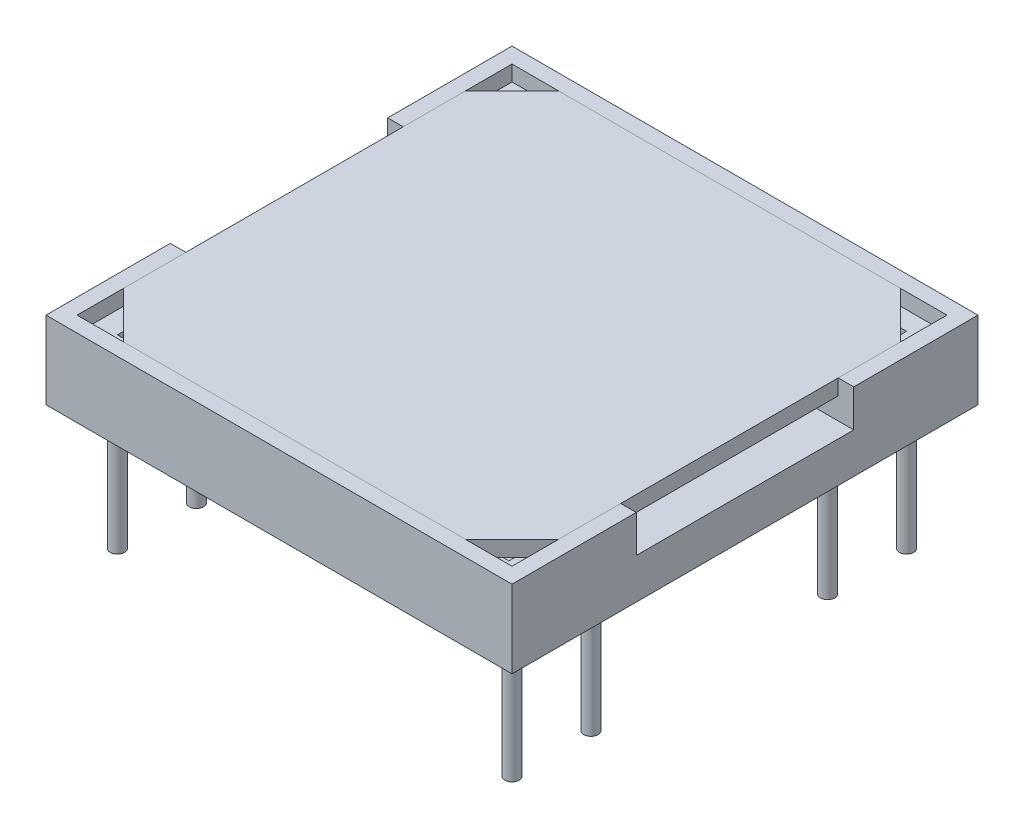
SolidWorks part; units mm, degrees
ref_plane "Front Plane" through (0, 0, 0) normal (0, 0, 1) x (1, 0, 0)
ref_plane "Top Plane" through (0, 0, 0) normal (0, 1, 0) x (1, 0, 0)
ref_plane "Right Plane" through (0, 0, 0) normal (1, 0, 0) x (0, 0, -1)
sketch "Sketch1" plane through (0, 0, 0) normal (0, 1, 0) x (1, 0, 0)
  line L0 (0, 0) -> (0, 7.5) construction
  line L1 (-7.5, -7.5) -> (7.5, -7.5)
  line L2 (-7.5, -7.5) -> (-7.5, 7.5)
  line L3 (-7.5, 7.5) -> (7.5, 7.5)
  line L4 (7.5, -7.5) -> (7.5, 7.5)
  line L5 (0, 0) -> (-7.5, 0) construction
  line L6 (-0.05, 6.4) -> (0, 6.4) construction
  line L7 (-6.3, 6.4) -> (-0.05, 6.4)
  line L8 (-6.3, 6.4) -> (-6.3, 0.05)
  line L9 (-6.3, 0.05) -> (-0.05, 0.05)
  line L10 (-0.05, 6.4) -> (-0.05, 0.05)
  line L23 (-6.3, 0.05) -> (-6.3, 0) construction
  line L24 (-6.1, 0.25) -> (-6.1, 0.05) construction
  line L25 (-6.3, 6.4) -> (-6.3, 7.5) construction
  line L26 (-6.1, 6.2) -> (-0.25, 6.2)
  line L27 (-6.1, 6.2) -> (-6.1, 0.25)
  line L28 (-6.1, 0.25) -> (-0.25, 0.25)
  line L29 (-0.25, 6.2) -> (-0.25, 0.25)
  line L30 (-0.25, 6.2) -> (-0.05, 6.2) construction
  line L31 (-0.25, -6.2) -> (-0.25, -0.25)
  line L32 (-6.1, -0.25) -> (-0.25, -0.25)
  line L33 (-6.1, -6.2) -> (-6.1, -0.25)
  line L34 (-6.1, -6.2) -> (-0.25, -6.2)
  line L35 (-0.05, -6.4) -> (-0.05, -0.05)
  line L36 (-6.3, -0.05) -> (-0.05, -0.05)
  line L37 (-6.3, -6.4) -> (-6.3, -0.05)
  line L38 (-6.3, -6.4) -> (-0.05, -6.4)
  line L39 (6.3, -6.4) -> (0.05, -6.4)
  line L40 (6.1, -6.2) -> (0.25, -6.2)
  line L41 (6.1, -0.25) -> (0.25, -0.25)
  line L42 (6.3, -0.05) -> (0.05, -0.05)
  line L43 (6.3, 0.05) -> (0.05, 0.05)
  line L44 (6.1, 0.25) -> (0.25, 0.25)
  line L45 (6.1, 6.2) -> (0.25, 6.2)
  line L46 (6.3, 6.4) -> (0.05, 6.4)
  line L47 (6.1, 6.2) -> (6.1, 0.25)
  line L48 (0.25, 6.2) -> (0.25, 0.25)
  line L49 (0.05, 6.4) -> (0.05, 0.05)
  line L50 (0.05, -6.4) -> (0.05, -0.05)
  line L51 (0.25, -6.2) -> (0.25, -0.25)
  line L52 (6.1, -6.2) -> (6.1, -0.25)
  line L53 (6.3, -6.4) -> (6.3, -0.05)
  line L54 (6.3, 6.4) -> (6.3, 0.05)
  line L55 (-7, -7) -> (-7, 7)
  line L56 (-7, 7) -> (7, 7)
  line L57 (-7, -7) -> (7, -7)
  line L58 (7, -7) -> (7, 7)
  line L59 (-7.5, 3.5) -> (-6.3, 3.5)
  line L60 (-7.5, -3.5) -> (-6.3, -3.5)
  line L61 (7.5, -3.5) -> (6.3, -3.5)
  line L62 (7.5, 3.5) -> (6.3, 3.5)
  line L63 (-6.3, 0.05) -> (-6.3, -0.05)
  line L64 (6.3, 0.05) -> (6.3, -0.05)
  line L65 (-0.05, 6.4) -> (0.05, 6.4)
  line L66 (-0.05, -6.4) -> (0.05, -6.4)
  point P49 (-7, 0)
  point P51 (0, -7)
  point P52 (0, 7)
  dimension "D1" = 7.5
  dimension "D2" = 7.5
  dimension "D3" = 0.2
  dimension "D4" = 0.25
  dimension "D5" = 0.2
  dimension "D6" = 6.35
  dimension "D7" = 6.25
  dimension "D8" = 0.25
  dimension "D9" = 5.95
  dimension "D10" = 5.85
  dimension "D11" = 7
  dimension "D12" = 7
  dimension "D13" = 3.5
extrude "Boss-Extrude1" add sketch "Sketch1" along normal blind 0.61 contours L2 L3 L4 L1
extrude "Boss-Extrude2" add sketch "Sketch1<3>" along normal blind 0.69 from surface contours L29 L26 L27 L28 | L45 L48 L44 L47 | L40 L52 L41 L51 | L33 L34 L31 L32 region at (-3.175, 0, -3.225) region at (-3.175, 0, 3.225) region at (3.175, 0, 3.225) region at (3.175, 0, -3.225) starting at face at (0, 0.61, 0)
sketch "Sketch1<3>" plane through (0, 0, 0) normal (0, 1, 0) x (1, 0, 0) same geometry as "Sketch1"
extrude "Boss-Extrude3" add sketch "Sketch1<4>" along normal blind 1.39 from surface contours L62 L4 L3 L2 L59 L55 L56 L58 | L7 L65 L46 L54 L62 L58 L56 L55 L59 L8 | L2 L60 L55 L59 | L63 L8 L59 L55 L60 L37 | L4 L61 L58 L57 L55 L60 L2 L1 | L66 L38 L37 L60 L55 L57 L58 L61 L53 L39 | L54 L64 L53 L61 L58 L62 | L4 L62 L58 L61 region at (-7.3448, 0, 5.5) region at (-7.25, 0, 0) region at (7.25, 0, 0) region at (-7.3448, 0, -5.5) region at (-6.65, 0, 3.6443) region at (-6.65, 0, 0) region at (6.65, 0, 0) region at (-6.8557, 0, -5.25) starting at face at (-3.175, 0.61, 3.225)
sketch "Sketch1<4>" plane through (0, 0, 0) normal (0, 1, 0) x (1, 0, 0) same geometry as "Sketch1"
extrude "Boss-Extrude4" add sketch "Sketch1<7>" along normal blind 0.5 from surface contours L62 L4 L3 L2 L59 L55 L56 L58 | L2 L60 L55 L59 | L4 L61 L58 L57 L55 L60 L2 L1 | L4 L62 L58 L61 region at (-7.3448, 0, 5.5) region at (-7.25, 0, 0) region at (7.25, 0, 0) region at (-7.3448, 0, -5.5) starting at face at (0, 2, 0)
sketch "Sketch1<7>" plane through (0, 0, 0) normal (0, 1, 0) x (1, 0, 0) same geometry as "Sketch1"
extrude "Cut-Extrude1" cut sketch "Sketch1<6>" against normal blind 1.2 from surface contours L2 L60 L55 L59 | L4 L62 L58 L61 | L63 L8 L59 L55 L60 L37 | L54 L64 L53 L61 L58 L62 region at (-7.25, 0, 0) region at (7.25, 0, 0) region at (-6.65, 0, 0) region at (6.65, 0, 0) starting at face at (0, 2.5, 0)
sketch "Sketch1<6>" plane through (0, 0, 0) normal (0, 1, 0) x (1, 0, 0) same geometry as "Sketch1"
sketch "Sketch2" plane through (0, 0, 0) normal (0, -1, 0) x (1, 0, 0)
  line L0 (0, 0) -> (0, 7.5) construction
  line L1 (-7.5, 7.5) -> (7.5, 7.5) construction
  line L2 (0, 0) -> (7.5, 0) construction
  line L3 (7.5, 7.5) -> (7.5, -7.5) construction
  line L4 (6.35, 6.35) -> (6.35, 3.81) construction
  line L5 (6.35, 3.81) -> (6.35, 0) construction
  circle A0 centre (6.35, 6.35) radius 0.23
  circle A1 centre (6.35, 3.81) radius 0.23
  circle A2 centre (-6.35, 3.81) radius 0.23
  circle A3 centre (-6.35, 6.35) radius 0.23
  circle A4 centre (6.35, -3.81) radius 0.23
  circle A5 centre (6.35, -6.35) radius 0.23
  circle A6 centre (-6.35, -6.35) radius 0.23
  circle A7 centre (-6.35, -3.81) radius 0.23
  dimension "D4" = 0.46
  dimension "D1" = 2.54
  dimension "D2" = 3.81
  dimension "D3" = 6.35
extrude "Boss-Extrude5" add sketch "Sketch2" along normal blind 4 contours A0 | A1 | A3 | A2 | A7 | A6 | A4 | A5
sketch "Sketch3" plane through (0, 2, 0) normal (0, 1, 0) x (1, 0, 0)
  line L0 (7, -5.5) -> (5.5, -7)
  line L1 (7, -7) -> (-7, -7)
  line L2 (7, -7) -> (7, 7)
  line L3 (7, 7) -> (-7, 7)
  line L4 (-7, -7) -> (-7, 7)
  line L5 (0, -7) -> (0, 7) construction
  line L6 (7, 0) -> (-7, 0) construction
  line L7 (7, 5.5) -> (5.5, 7)
  line L8 (-7, 5.5) -> (-5.5, 7)
  line L9 (-7, -5.5) -> (-5.5, -7)
  line M10 (-6.3, -6.4) -> (-6.3, -3.5)
  line M11 (-6.3, -3.5) -> (-7, -3.5)
  line M12 (-7, -3.5) -> (-7, -7)
  line M14 (7, -7) -> (7, -3.5)
  line M15 (7, -3.5) -> (6.3, -3.5)
  line M16 (6.3, -3.5) -> (6.3, -6.4)
  line M17 (6.3, -6.4) -> (-6.3, -6.4)
  dimension "D1" = 1.5
  dimension "D2" = 1.5
extrude "Boss-Extrude6" add sketch "Sketch3" along normal blind 0.5 separate body contours L0 M14 M15 M16 | L9 L0 L2 L7 L3 L8 L4 M10 M17 M16 M15 M11 | L9 L1 L0 M17 | L9 M12 M10 M11 region at (6.6326, 2, 4.6837) region at (0, 2, -0.3421) region at (0, 2, 6.6948) region at (-6.6326, 2, 4.6837)
